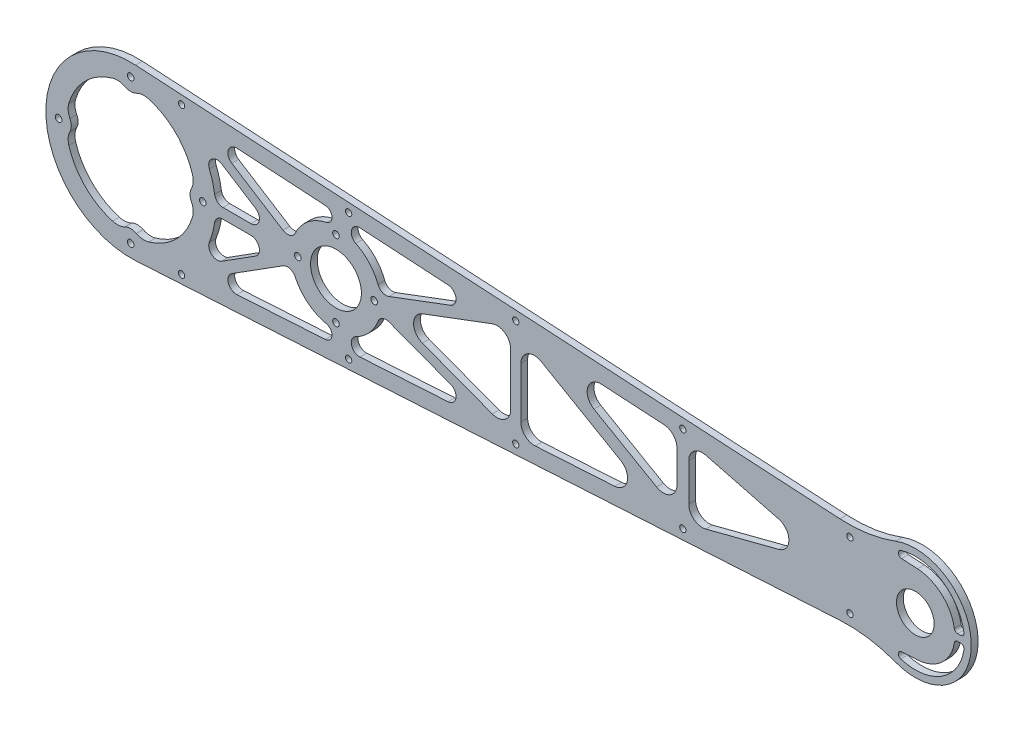
SolidWorks part; units mm, degrees
ref_plane "Front Plane" through (0, 0, 0) normal (0, 0, 1) x (1, 0, 0)
ref_plane "Top Plane" through (0, 0, 0) normal (0, 1, 0) x (1, 0, 0)
ref_plane "Right Plane" through (0, 0, 0) normal (1, 0, 0) x (0, 0, -1)
sketch "Sketch1" plane through (0, 0, 0) normal (0, 0, 1) x (1, 0, 0)
  line L0 (-231.25, 0) -> (231.25, 0) construction
  line L1 (-228.3622, 49.9165) -> (232.595, 23.2486)
  line L2 (-228.3622, -49.9165) -> (232.595, -23.2486)
  line L3 (191.25, 20.6322) -> (-201.25, 43.3396) construction
  circle A0 centre (231.25, 0) radius 11.1125
  arc A1 (232.595, 23.2486) -> (232.595, -23.2486) centre (231.25, 0) cw
  circle A2 centre (-231.25, 0) radius 42.5 construction
  circle A3 centre (-110.25, 0) radius 22.5 construction
  arc A4 (-228.3622, 49.9165) -> (-228.3622, -49.9165) centre (-231.25, 0) ccw
  circle A5 centre (-231.25, 42.5) radius 1.75 construction
  circle A6 centre (-231.25, 0) radius 30
  circle A7 centre (-110.25, 0) radius 15
  circle A8 centre (231.25, 0) radius 35.306 construction
  circle A9 centre (-201.25, 43.3396) radius 1.85
  circle A10 centre (-102.7635, 37.3743) radius 1.85
  circle A11 centre (-4.277, 31.4089) radius 1.85
  circle A12 centre (94.2095, 25.4436) radius 1.85
  circle A13 centre (192.696, 19.4782) radius 1.85
  circle A14 centre (291.1825, 13.5129) radius 1.85 construction
  circle A15 centre (192.696, -19.4782) radius 1.85
  circle A16 centre (94.2095, -25.4436) radius 1.85
  circle A17 centre (-4.277, -31.4089) radius 1.85
  circle A18 centre (-102.7635, -37.3743) radius 1.85
  circle A19 centre (-201.25, -43.3396) radius 1.85
  point P4 (0, 0)
  point P15 (-231.25, 44.25)
  point P16 (-273.75, 0)
  point P17 (-231.25, 50)
  point P18 (-110.25, 22.5)
  point P19 (-231.25, -42.5)
  point P20 (-188.75, 0)
  point P21 (-132.75, 0)
  point P22 (-110.25, -22.5)
  point P23 (-87.75, 0)
  dimension "D2" = 22.225
  dimension "D3" = 85
  dimension "D5" = 45
  dimension "D6" = 3.5
  dimension "D7" = 7.5
  dimension "D8" = 23.2875
  dimension "D9" = 60
  dimension "D10" = 30
  dimension "D11" = 70.612
  dimension "D13" = 3.7
  dimension "D16" = 6
  dimension "D1" = 462.5
  dimension "D4" = 121
  dimension "D12" = 5
  dimension "D14" = 30
  dimension "D15" = 40
extrude "Boss-Extrude1" add sketch "Sketch1" along normal blind 4
sketch "Sketch4" plane through (0, 0, 4) normal (0, 0, 1) x (1, 0, 0)
  point P0 (-231.25, 42.5)
  point P7 (-188.75, 0)
  point P10 (-132.75, 0)
  point P13 (-110.25, 22.5)
  point P16 (-87.75, 0)
  point P19 (-110.25, -22.5)
  point P24 (-273.75, 0)
  point P28 (-231.25, -42.5)
hole_wizard "M3.5 Clearance Hole1" positions "Sketch4" profile "Sketch6" hole size "M3.5" standard "ANSI Metric" end condition up to next
sketch "Sketch6" plane through (-231.25, 42.5, 4) normal (1, 0, 0) x (0, -1, 0)
  line L0 (0, 0) -> (0, 4)
  line L1 (0, 4) -> (1.95, 4)
  line L2 (1.95, 4) -> (1.95, 0)
  line L5 (1.95, 0) -> (0, 0)
  line L11 (0, -6.35) -> (0, 107.95) construction
  dimension "Thru Hole Dia." = 3.9
  dimension "Thru Hole Depth" = 4
sketch "Sketch7" plane through (0, 0, 4) normal (0, 0, 1) x (1, 0, 0)
  line L0 (94.2095, 25.4436) -> (94.2095, -25.4436) construction
  line L1 (94.2095, -25.4436) -> (192.696, 0) construction
  line L2 (192.696, 0) -> (94.2095, 25.4436) construction
  line L3 (192.696, 0) -> (-87.75, 0) construction
  line L4 (192.696, -19.4782) -> (192.696, 19.4782) construction
  line L5 (107.7105, 18.8571) -> (150.7205, 7.7457)
  line L6 (150.7205, -7.7457) -> (107.7105, -18.8571)
  line L7 (97.7095, -11.1115) -> (97.7095, 11.1115)
  line L8 (-4.277, -31.4089) -> (-4.277, 31.4089) construction
  line L9 (-4.277, 31.4089) -> (94.2095, -25.4436) construction
  line L10 (-4.277, 31.4089) -> (94.2095, 25.4436) construction
  line L11 (-4.277, -31.4089) -> (94.2095, -25.4436) construction
  line L12 (-87.75, 0) -> (-102.7635, 37.3743) construction
  line L13 (-102.7635, 37.3743) -> (-4.277, 31.4089) construction
  line L14 (-4.277, 31.4089) -> (-87.75, 0) construction
  line L15 (90.7095, -4.9492) -> (90.7095, 14.1182)
  line L16 (83.1932, 22.1035) -> (46.2904, 24.3387)
  line L17 (41.8072, 9.4249) -> (78.7099, -11.8777)
  line L18 (10.7225, 18.1316) -> (57.6374, -8.9506)
  line L19 (54.1216, -23.8644) -> (7.2067, -26.706)
  line L20 (-1.277, -18.7207) -> (-1.277, 11.2032)
  line L22 (-228.3622, -49.9165) -> (232.595, -23.2486) construction
  line L23 (-7.277, -15.517) -> (-7.277, 15.517)
  line L24 (-18.0944, 23.0044) -> (-59.3325, 7.4875)
  line L25 (-59.3325, -7.4875) -> (-18.0944, -23.0044)
  line L27 (-79.0341, 6.4849) -> (-42.7227, 20.1481)
  line L28 (-44.1812, 29.8186) -> (-96.0994, 32.9633)
  line L32 (-132.75, 0) -> (-188.75, 0) construction
  line L33 (-188.75, 0) -> (-201.25, 43.3396) construction
  line L34 (-201.25, 43.3396) -> (-132.75, 0) construction
  line L35 (-132.75, 0) -> (-102.7635, 37.3743) construction
  line L36 (-102.7635, 37.3743) -> (-201.25, 43.3396) construction
  line L37 (-171.617, 28.141) -> (-141.4788, 9.0727)
  line L39 (-116.5248, 34.2005) -> (-168.6414, 37.3572)
  line L41 (-176.8349, 3) -> (-160.3569, 3)
  line L42 (-157.6835, 12.2253) -> (-177.574, 24.8099)
  line L44 (-116.5248, -34.2005) -> (-168.6414, -37.3572)
  line L45 (-171.617, -28.141) -> (-141.4788, -9.0727)
  line L46 (-157.6835, -12.2253) -> (-177.574, -24.8099)
  line L48 (-176.8349, -3) -> (-160.3569, -3)
  line L50 (-44.1812, -29.8186) -> (-96.0994, -32.9633)
  line L51 (-79.0341, -6.4849) -> (-42.7227, -20.1481)
  line L52 (-102.7635, -37.3743) -> (-110.25, -22.5) construction
  line L53 (-113.0228, -28.1124) -> (-105.6224, -42.8156) construction
  line L54 (-100.7253, -30.3024) -> (-94.7439, -42.1863) construction
  arc A0 (150.7205, 7.7457) -> (150.7205, -7.7457) centre (148.7195, 0) cw
  arc A1 (107.7105, -18.8571) -> (97.7095, -11.1115) centre (105.7095, -11.1115) cw
  arc A2 (107.7105, 18.8571) -> (97.7095, 11.1115) centre (105.7095, 11.1115) ccw
  arc A3 (90.7095, 14.1182) -> (83.1932, 22.1035) centre (82.7095, 14.1182) ccw
  arc A4 (46.2904, 24.3387) -> (41.8072, 9.4249) centre (45.8067, 16.3534) ccw
  arc A5 (90.7095, -4.9492) -> (78.7099, -11.8777) centre (82.7095, -4.9492) cw
  arc A6 (57.6374, -8.9506) -> (54.1216, -23.8644) centre (53.6379, -15.879) cw
  arc A7 (7.2067, -26.706) -> (-1.277, -18.7207) centre (6.723, -18.7207) cw
  arc A8 (10.7225, 18.1316) -> (-1.277, 11.2032) centre (6.723, 11.2032) ccw
  arc A9 (-7.277, -15.517) -> (-18.0944, -23.0044) centre (-15.277, -15.517) cw
  arc A10 (-7.277, 15.517) -> (-18.0944, 23.0044) centre (-15.277, 15.517) ccw
  arc A11 (-59.3325, 7.4875) -> (-59.3325, -7.4875) centre (-56.5152, 0) ccw
  arc A12 (-42.7227, 20.1481) -> (-44.1812, 29.8186) centre (-44.4835, 24.8278) ccw
  arc A18 (-171.617, 28.141) -> (-168.6414, 37.3572) centre (-168.9437, 32.3663) cw
  arc A21 (-160.3569, 3) -> (-157.6835, 12.2253) centre (-160.3569, 8) ccw
  arc A22 (-181.7818, 7.2727) -> (-176.8349, 3) centre (-176.8349, 8) ccw
  arc A23 (-184.8839, 18.7133) -> (-177.574, 24.8099) centre (-180.2473, 20.5846) cw
  arc A26 (-171.617, -28.141) -> (-168.6414, -37.3572) centre (-168.9437, -32.3663) ccw
  arc A27 (-184.8839, -18.7133) -> (-177.574, -24.8099) centre (-180.2473, -20.5846) ccw
  arc A28 (-181.7818, -7.2727) -> (-176.8349, -3) centre (-176.8349, -8) cw
  arc A29 (-160.3569, -3) -> (-157.6835, -12.2253) centre (-160.3569, -8) cw
  circle A30 centre (-110.25, 0) radius 15 construction
  circle A31 centre (-110.25, 0) radius 15 construction
  circle A32 centre (-110.25, 0) radius 22.5 construction
  arc A34 (-85.4703, 9.3925) -> (-98.5366, 23.7707) centre (-110.25, 0) ccw
  arc A37 (-85.4703, 9.3925) -> (-79.0341, 6.4849) centre (-80.7949, 11.1646) ccw
  arc A38 (-42.7227, -20.1481) -> (-44.1812, -29.8186) centre (-44.4835, -24.8278) cw
  arc A39 (-96.0994, -32.9633) -> (-98.5366, -23.7707) centre (-96.3927, -28.1217) cw
  arc A40 (-134.2728, 11.1872) -> (-115.8848, 25.894) centre (-110.25, 0) cw
  arc A41 (-85.4703, -9.3925) -> (-98.5366, -23.7707) centre (-110.25, 0) cw
  arc A42 (-85.4703, -9.3925) -> (-79.0341, -6.4849) centre (-80.7949, -11.1646) cw
  arc A43 (-116.5248, 34.2005) -> (-115.8848, 25.894) centre (-116.779, 30.003) cw
  arc A44 (-134.2728, 11.1872) -> (-141.4788, 9.0727) centre (-138.8054, 13.298) cw
  arc A45 (-116.5248, -34.2005) -> (-115.8848, -25.894) centre (-116.779, -30.003) ccw
  arc A46 (-134.2728, -11.1872) -> (-115.8848, -25.894) centre (-110.25, 0) ccw
  arc A47 (-134.2728, -11.1872) -> (-141.4788, -9.0727) centre (-138.8054, -13.298) ccw
  arc A48 (-96.0994, 32.9633) -> (-98.5366, 23.7707) centre (-96.3927, 28.1217) ccw
  circle A49 centre (-4.277, -31.4089) radius 1.85 construction
  circle A50 centre (-4.277, -31.4089) radius 1.85
  arc A51 (-184.8839, 18.7133) -> (-181.7818, 7.2727) centre (-231.25, 0) cw
  arc A52 (-228.3622, 49.9165) -> (-228.3622, -49.9165) centre (-231.25, 0) ccw construction
  arc A53 (-228.3622, 49.9165) -> (-228.3622, -49.9165) centre (-231.25, 0) ccw
  arc A55 (-184.8839, -18.7133) -> (-181.7818, -7.2727) centre (-231.25, 0) ccw
  point P36 (180.7024, 0)
  point P59 (-79.2314, 0)
  point P102 (-113.0228, -28.1124)
  dimension "D8" = 8
  dimension "D11" = 5
  dimension "D12" = 5
  dimension "D18" = 5
  dimension "D19" = 5
  dimension "D10" = 4
  dimension "D21" = 5
  dimension "D1" = 3
  dimension "D2" = 7
  dimension "D3" = 8
  dimension "D4" = 8
  dimension "D5" = 8
  dimension "D6" = 6
  dimension "D7" = 6
  dimension "D9" = 8
  dimension "D13" = 8
  dimension "D14" = 5
  dimension "D15" = 6
  dimension "D17" = 6
extrude "Cut-Extrude1" cut sketch "Sketch7" against normal blind 10 contours A55 A27 L46 A29 L48 A28 | A23 A51 A22 L41 A21 L42 | A44 A40 A43 L39 A18 L37 | A46 A47 L45 A26 L44 A45 | A42 A41 A39 L50 A38 L51 | L28 A48 A34 A37 L27 A12 | L24 A11 L25 A9 L23 A10 | L18 A8 L20 A7 L19 A6 | L5 A2 L7 A1 L6 A0 | A5 L15 A3 L16 A4 L17 region at (122.1459, 0, 4) region at (68.375, 8.863, 4) region at (24.042, -7.8996, 4) region at (-30.0623, 0, 4) region at (-71.6765, 22.0808, 4) region at (-143.7382, 26.1619, 4) region at (-171.7996, 12.3824, 4) region at (-143.7382, -26.1619, 4) region at (-171.7996, -12.3824, 4) region at (-71.6765, -22.0808, 4)
sketch "Sketch8" plane through (0, 0, 4) normal (0, 0, 1) x (1, 0, 0)
  arc A0 (-267.0517, -3.3738) -> (-267.0517, 3.3738) centre (-273.75, 0) ccw
  arc A1 (-267.7172, 10.6837) -> (-241.9337, 36.4672) centre (-231.25, 0) cw
  arc A2 (-228.3622, 49.9165) -> (-228.3622, -49.9165) centre (-231.25, 0) ccw construction
  arc A3 (-228.3622, 49.9165) -> (-228.3622, -49.9165) centre (-231.25, 0) ccw
  circle A4 centre (-273.75, 0) radius 1.95 construction
  circle A5 centre (-273.75, 0) radius 1.95
  arc A6 (-234.6238, 35.8017) -> (-227.8762, 35.8017) centre (-231.25, 42.5) ccw
  arc A7 (-220.5663, 36.4672) -> (-194.7828, 10.6837) centre (-231.25, 0) cw
  arc A8 (-195.4483, 3.3738) -> (-195.4483, -3.3738) centre (-188.75, 0) ccw
  arc A9 (-194.7828, -10.6837) -> (-220.5663, -36.4672) centre (-231.25, 0) cw
  arc A10 (-227.8762, -35.8017) -> (-234.6238, -35.8017) centre (-231.25, -42.5) ccw
  arc A11 (-241.9337, -36.4672) -> (-267.7172, -10.6837) centre (-231.25, 0) cw
  arc A12 (-241.9337, 36.4672) -> (-234.6238, 35.8017) centre (-239.1222, 26.8706) cw
  arc A13 (-227.8762, 35.8017) -> (-220.5663, 36.4672) centre (-223.3778, 26.8706) cw
  arc A14 (-194.7828, 10.6837) -> (-195.4483, 3.3738) centre (-204.3794, 7.8722) cw
  arc A15 (-195.4483, -3.3738) -> (-194.7828, -10.6837) centre (-204.3794, -7.8722) cw
  arc A16 (-220.5663, -36.4672) -> (-227.8762, -35.8017) centre (-223.3778, -26.8706) cw
  arc A17 (-234.6238, -35.8017) -> (-241.9337, -36.4672) centre (-239.1222, -26.8706) cw
  arc A18 (-267.0517, -3.3738) -> (-267.7172, -10.6837) centre (-258.1206, -7.8722) ccw
  arc A19 (-267.0517, 3.3738) -> (-267.7172, 10.6837) centre (-258.1206, 7.8722) cw
  point P24 (-231.25, 0)
  dimension "D1" = 12
  dimension "D3" = 10
  dimension "D2" = 4
extrude "Cut-Extrude2" cut sketch "Sketch8" against normal blind 10 contours A11 A10 A9 A8 A7 A6 A1 A0 region at (-231.25, 0, 4)
sketch "Sketch9" plane through (0, 0, 4) normal (0, 0, 1) x (1, 0, 0)
  line L2 (232.595, 23.2486) -> (-228.3622, 49.9165) construction
  line L3 (-228.3622, -49.9165) -> (232.595, -23.2486) construction
  line L4 (254.5375, 0) -> (264.25, 0) construction
  line L5 (254.4515, 2) -> (260.181, 2)
  line L6 (254.4515, -2) -> (260.181, -2)
  line L7 (215.3411, 24.2468) -> (209.2526, 24.5991)
  line L8 (215.3411, -24.2468) -> (209.2526, -24.5991)
  arc A1 (209.2526, -24.5991) -> (209.2526, 24.5991) centre (231.25, 0) ccw
  arc A2 (232.595, -23.2486) -> (232.595, 23.2486) centre (231.25, 0) ccw construction
  arc A3 (254.4515, -2) -> (254.4515, 2) centre (231.25, 0) ccw
  arc A4 (215.3411, 24.2468) -> (260.181, 2) centre (231.25, 0) cw
  arc A5 (260.181, -2) -> (215.3411, -24.2468) centre (231.25, 0) cw
  dimension "D1" = 33
  dimension "D2" = 4
  dimension "D3" = 4
extrude "Boss-Extrude2" add sketch "Sketch9" against normal up to surface (4 mm away) up to face at (119.0803, 0, 0)
fillet "Fillet1" radius 2 6 edges at (215.3411, -24.2468, 2) (254.4515, -2, 2) (260.181, -2, 2) (254.4515, 2, 2) (260.181, 2, 2) (215.3411, 24.2468, 2)
fillet "Fillet2" radius 80 2 edges at (209.2526, 24.5991, 2) (209.2526, -24.5991, 2)
